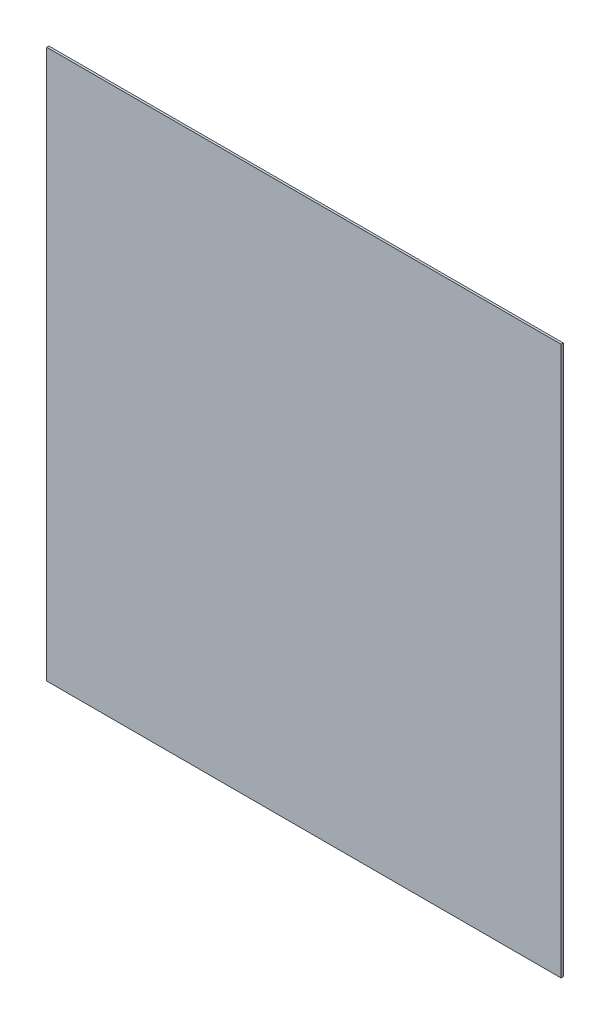
SolidWorks part; units mm, degrees
material "Mahogany"
ref_plane "Front Plane" through (0, 0, 0) normal (0, 0, 1) x (1, 0, 0)
ref_plane "Top Plane" through (0, 0, 0) normal (0, 1, 0) x (1, 0, 0)
ref_plane "Right Plane" through (0, 0, 0) normal (1, 0, 0) x (0, 0, -1)
sketch "Sketch1" plane through (0, 0, 0) normal (0, 0, 1) x (1, 0, 0)
  line L1 (-372.5, 397.5) -> (372.5, 397.5)
  line L2 (-372.5, 397.5) -> (-372.5, -397.5)
  line L3 (-372.5, -397.5) -> (372.5, -397.5)
  line L4 (372.5, 397.5) -> (372.5, -397.5)
  line L5 (-372.5, 397.5) -> (372.5, -397.5) construction
  line L6 (-372.5, -397.5) -> (372.5, 397.5) construction
  point P0 (0, 0)
  dimension "D1" = 745
  dimension "D2" = 795
extrude "Boss-Extrude1" add sketch "Sketch1" along normal blind 3.175
equation "\"W\"= 1700"
equation "\"L\"= 760"
equation "\"H\"= 810"
equation "\"ARM_BOLT_SPACING\"= 140"
equation "\"ARM_TO_WALL\"= 300"
equation "\"D1@Sketch1\"=\"L\"-15"
equation "\"D2@Sketch1\"=\"H\"-(15)"
